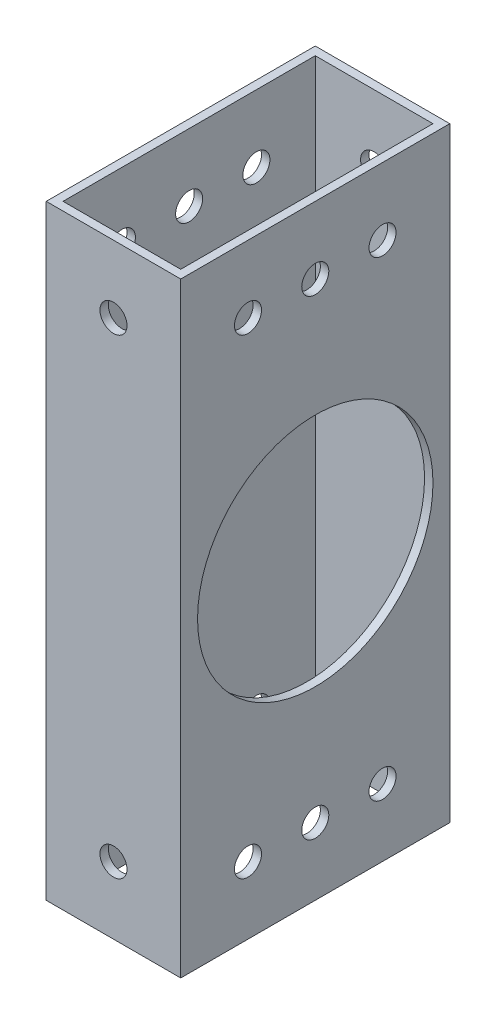
SolidWorks part; units mm, degrees
material "6061-T6 (SS)"
ref_plane "Front" through (0, 0, 0) normal (0, 0, 1) x (1, 0, 0)
ref_plane "Top" through (0, 0, 0) normal (0, 1, 0) x (1, 0, 0)
ref_plane "Right" through (0, 0, 0) normal (1, 0, 0) x (0, 0, -1)
sketch "Sketch1" plane through (0, 0, 0) normal (0, 1, 0) x (1, 0, 0)
  line L1 (12.7, 25.4) -> (-12.7, 25.4)
  line L2 (12.7, 25.4) -> (12.7, -25.4)
  line L3 (12.7, -25.4) -> (-12.7, -25.4)
  line L4 (-12.7, 25.4) -> (-12.7, -25.4)
  line L5 (12.7, 25.4) -> (-12.7, -25.4) construction
  line L6 (12.7, -25.4) -> (-12.7, 25.4) construction
  point P0 (0, 0)
  dimension "D1" = 25.4
  dimension "D2" = 50.8
extrude "Extrude-Thin1" add sketch "Sketch1" along normal up to surface (114.3 mm away) thin thin type one direction reverse wall 1.5875
sketch "Sketch4" plane through (-12.7, 0, 0) normal (-1, 0, 0) x (0, 0, 1)
  line L0 (-12.7, 12.7) -> (12.7, 12.7) construction
  line L3 (-12.7, 101.6) -> (12.7, 101.6) construction
  line L5 (-25.4, 0) -> (25.4, 0) construction
  line L6 (-25.4, 114.3) -> (25.4, 114.3) construction
  point P0 (-12.7, 101.6)
  point P2 (0, 101.6)
  point P4 (12.7, 101.6)
  point P6 (-12.7, 12.7)
  point P8 (0, 12.7)
  point P10 (12.7, 12.7)
  dimension "D1" = 12.7
  dimension "D2" = 12.7
  dimension "D3" = 12.7
  dimension "D4" = 12.7
hole_wizard "#10 Clearance Hole1" positions "Sketch4" profile "Sketch3" hole size "#10" standard "ANSI Inch" end condition through all
sketch "Sketch3" plane through (-12.7, 101.6, -12.7) normal (0, 1, 0) x (0, 0, 1)
  line L0 (0, 0) -> (0, 25.4)
  line L1 (0, 25.4) -> (2.5527, 25.4)
  line L2 (2.5527, 25.4) -> (2.5527, 0)
  line L5 (2.5527, 0) -> (0, 0)
  line L11 (0, -6.35) -> (0, 107.95) construction
  dimension "Thru Hole Dia." = 5.1054
  dimension "Thru Hole Depth" = 25.4
sketch "Sketch7" plane through (0, 0, 25.4) normal (0, 0, 1) x (1, 0, 0)
  line L0 (-12.7, 0) -> (12.7, 0) construction
  line L1 (-12.7, 114.3) -> (12.7, 114.3) construction
  point P0 (0, 12.7)
  point P2 (0, 101.6)
  dimension "D1" = 12.7
  dimension "D2" = 12.7
hole_wizard "#10 Clearance Hole2" positions "Sketch7" profile "Sketch6" hole size "#10" standard "ANSI Inch" end condition through all
sketch "Sketch6" plane through (0, 12.7, 25.4) normal (1, 0, 0) x (0, -1, 0)
  line L0 (0, 0) -> (0, 50.8)
  line L1 (0, 50.8) -> (2.5527, 50.8)
  line L2 (2.5527, 50.8) -> (2.5527, 0)
  line L5 (2.5527, 0) -> (0, 0)
  line L11 (0, -6.35) -> (0, 107.95) construction
  dimension "Thru Hole Dia." = 5.1054
  dimension "Thru Hole Depth" = 50.8
sketch "Sketch8" plane through (-12.7, 0, 0) normal (-1, 0, 0) x (0, 0, 1)
  line L0 (-25.4, 0) -> (25.4, 114.3) construction
  line L1 (25.4, 114.3) -> (25.4, 0) construction
  line L2 (-25.4, 114.3) -> (25.4, 114.3) construction
  line L3 (-25.4, 114.3) -> (-25.4, 0) construction
  line L4 (-25.4, 0) -> (25.4, 0) construction
  line L5 (10.8183, 59.69) -> (13.0175, 59.69)
  line L7 (13.0175, 54.61) -> (10.8183, 54.61)
  arc A0 (10.8183, 59.69) -> (10.8183, 54.61) centre (0, 57.15) ccw
  arc A1 (13.0175, 59.69) -> (13.0175, 54.61) centre (13.0175, 57.15) cw
  point P10 (12.2095, 55.0012)
  point P16 (11.7312, 59.0705)
  point P19 (0, 0)
  dimension "D1" = 22.225
  dimension "D2" = 4.445
  dimension "D3" = 5.08
extrude "Cut-Extrude1" cut sketch "Sketch8" against normal through all
sketch "Sketch9" plane through (12.7, 0, 0) normal (1, 0, 0) x (0, 0, -1)
  circle A0 centre (0, 57.15) radius 22.225
  circle A1 centre (0, 57.15) radius 11.1125 construction
  dimension "D1" = 44.45
extrude "Cut-Extrude2" cut sketch "Sketch9" against normal up to next
